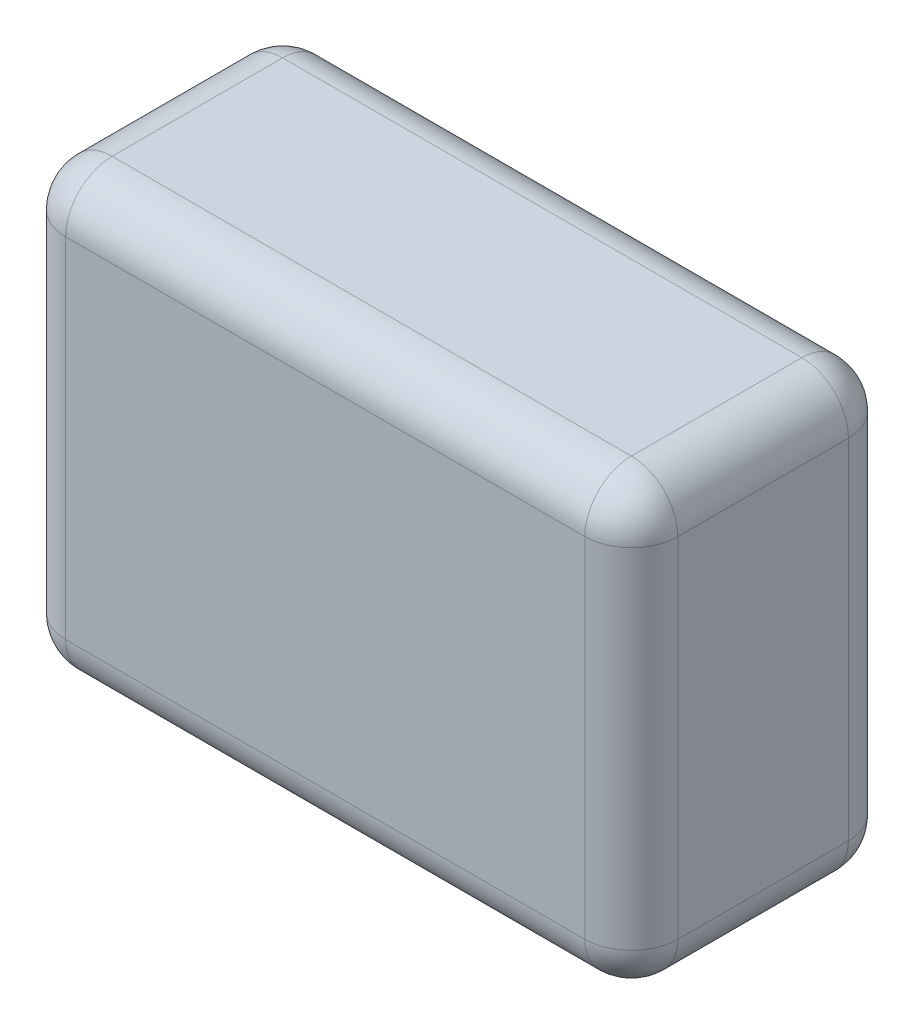
SolidWorks part; units mm, degrees
ref_plane "Front Plane" through (0, 0, 0) normal (0, 0, 1) x (1, 0, 0)
ref_plane "Top Plane" through (0, 0, 0) normal (0, 1, 0) x (1, 0, 0)
ref_plane "Right Plane" through (0, 0, 0) normal (1, 0, 0) x (0, 0, -1)
sketch "Sketch1" plane through (0, 0, 0) normal (0, 1, 0) x (1, 0, 0)
  line L1 (0, 0) -> (79, 0)
  line L2 (0, 0) -> (0, -34)
  line L3 (0, -34) -> (79, -34)
  line L4 (79, 0) -> (79, -34)
  dimension "D1" = 79
  dimension "D2" = 34
extrude "Boss-Extrude1" add sketch "Sketch1" along normal blind 57
fillet "Fillet1" radius 6 12 edges at (0, 28.5, 34) (79, 28.5, 34) (79, 28.5, 0) (0, 28.5, 0) (39.5, 57, 0) (79, 57, 17) (39.5, 57, 34) (0, 57, 17) (39.5, 0, 0) (79, 0, 17) (39.5, 0, 34) (0, 0, 17)
